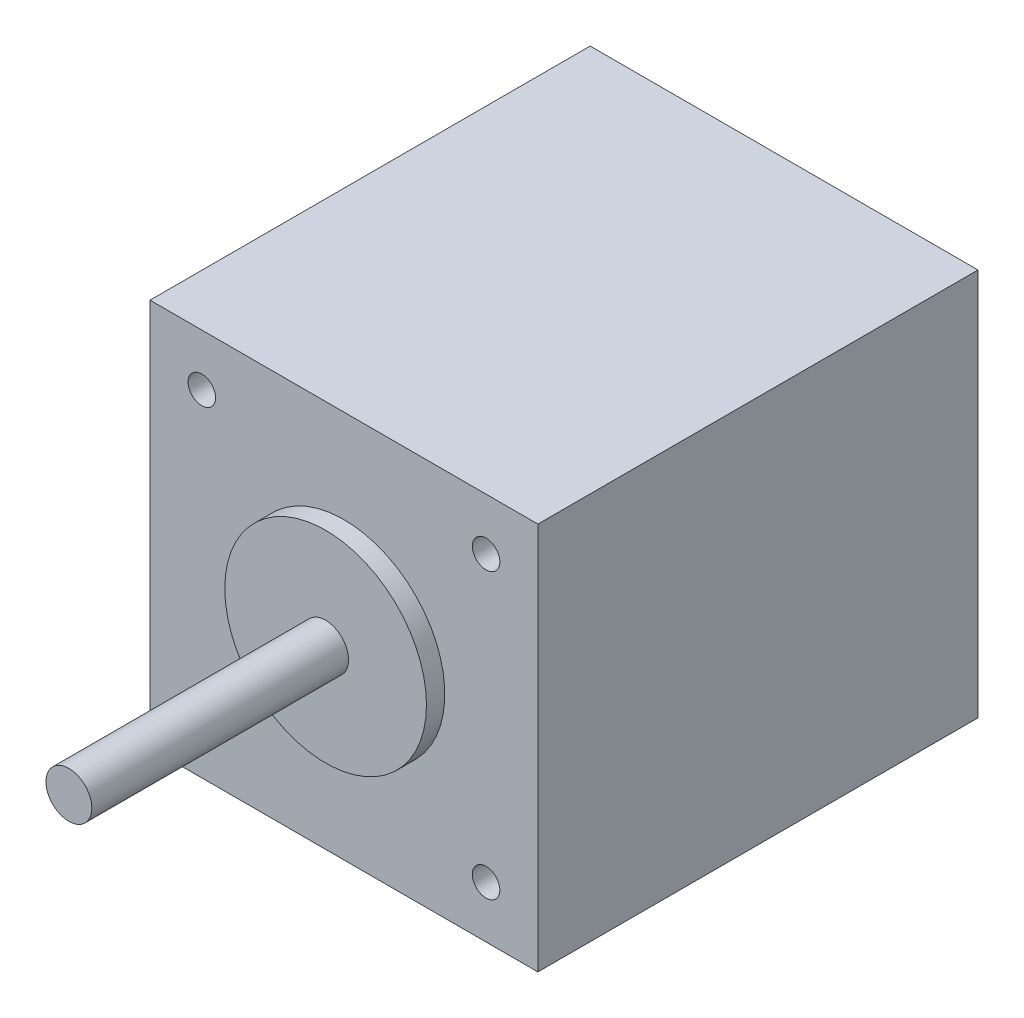
SolidWorks part; units mm, degrees
ref_plane "Спереди" through (0, 0, 0) normal (0, 0, 1) x (1, 0, 0)
ref_plane "Сверху" through (0, 0, 0) normal (0, 1, 0) x (1, 0, 0)
ref_plane "Справа" through (0, 0, 0) normal (1, 0, 0) x (0, 0, -1)
other "Configuration Table"
sketch "Эскиз1" plane through (0, 0, 0) normal (0, 0, 1) x (1, 0, 0)
  line L1 (-21.15, -21.15) -> (21.15, -21.15)
  line L2 (-21.15, -21.15) -> (-21.15, 21.15)
  line L3 (-21.15, 21.15) -> (21.15, 21.15)
  line L4 (21.15, -21.15) -> (21.15, 21.15)
  line L5 (-21.15, -21.15) -> (21.15, 21.15) construction
  line L6 (-21.15, 21.15) -> (21.15, -21.15) construction
  point P0 (0, 0)
  dimension "D1" = 42.3
  dimension "D2" = 42.3
extrude "Корпус" add sketch "Эскиз1" along normal blind 48
sketch "Эскиз2" plane through (0, 0, 0) normal (0, 0, 1) x (1, 0, 0)
  circle A0 centre (0, 0) radius 2.5
extrude "Вал_ПРЕДВ" add sketch "Эскиз2" along normal blind 78
sketch "Эскиз3" plane through (0, 0, 0) normal (0, 0, 1) x (1, 0, 0)
  circle A0 centre (0, 0) radius 11
  dimension "D1" = 22
extrude "Буртик_ПРЕДВ" add sketch "Эскиз3" along normal blind 50
sketch "Эскиз4" plane through (0, 0, 0) normal (0, 0, 1) x (1, 0, 0)
  circle A0 centre (0, 0) radius 8
  dimension "D1" = 16
sketch "Эскиз5" plane through (0, 0, 0) normal (0, 0, 1) x (1, 0, 0)
  circle A0 centre (-15.5, -15.5) radius 1.5
  circle A1 centre (-15.5, 15.5) radius 1.5
  circle A2 centre (15.5, -15.5) radius 1.5
  circle A3 centre (15.5, 15.5) radius 1.5
  dimension "D2" = 3
  dimension "D3" = 3
  dimension "D4" = 3
extrude "Крепеж_М3_ПРЕДВ" cut sketch "Эскиз5" against normal blind 4.5 from offset 48
equation "\"Мотор X ширина корпуса\"= 42.3"
equation "\"Мотор X высота корпуса\"= 42.3"
equation "\"Мотор X длина корпуса\"= 40"
equation "\"Мотор X вылет вала\"= 19.8"
equation "\"Мотор Y ширина корпуса\"= 42.3"
equation "\"Мотор Y высота корпуса\"= 42.3"
equation "\"Мотор Y длина корпуса\"= 48"
equation "\"Мотор Y вылет вала\"= 30"
equation "\"Мотор Z ширина корпуса\"= 42"
equation "\"Мотор Z высота корпуса\"= 42"
equation "\"Мотор Z длина корпуса\"= 40"
equation "\"Мотор Z вылет вала\"= 23"
equation "\"Мотор диаметр вала ПРЕДВ\"= 5"
equation "\"Мотор шаг крепления ПРЕДВ\"= 31"
equation "\"Мотор диаметр отверстий ПРЕДВ\"= 3"
equation "\"Мотор глубина отверстий ПРЕДВ\"= 4.5"
equation "\"Мотор диаметр буртика ПРЕДВ\"= 22"
equation "\"Мотор высота буртика ПРЕДВ\"= 2"
equation "\"Мотор диаметр шкива ПРЕДВ\"= 16"
equation "\"Мотор длина шкива ПРЕДВ\"= 12"
equation "\"Мотор отступ шкива ПРЕДВ\"= 5"
equation "\"Мотор X шаг градусов\"= 1.8"
equation "\"Мотор Y шаг градусов\"= 1.8"
equation "\"Мотор Z шаг градусов\"= 1.8"
equation "\"Мотор Y диаметр ротора\"= 25.78"
equation "\"D1@Эскиз1\" = \"Мотор Y ширина корпуса\""
equation "\"D1@Корпус\" = \"Мотор Y длина корпуса\""
equation "\"D1@Эскиз2\" = \"Мотор диаметр вала ПРЕДВ\""
equation "\"D1@Вал_ПРЕДВ\" = \"Мотор Y длина корпуса\" + \"Мотор Y вылет вала\""
equation "\"D1@Эскиз3\" = \"Мотор диаметр буртика ПРЕДВ\""
equation "\"D1@Буртик_ПРЕДВ\" = \"Мотор Y длина корпуса\" + \"Мотор высота буртика ПРЕДВ\""
equation "\"D1@Эскиз4\" = \"Мотор диаметр шкива ПРЕДВ\""
equation "\"D1@Эскиз5\" = \"Мотор диаметр отверстий ПРЕДВ\""
equation "\"D2@Эскиз5\" = \"Мотор диаметр отверстий ПРЕДВ\""
equation "\"D3@Эскиз5\" = \"Мотор диаметр отверстий ПРЕДВ\""
equation "\"D4@Эскиз5\" = \"Мотор диаметр отверстий ПРЕДВ\""
equation "\"D1@Крепеж_М3_ПРЕДВ\" = \"Мотор глубина отверстий ПРЕДВ\""
equation "\"D19@Крепеж_М3_ПРЕДВ\" = \"Мотор Y длина корпуса\""
equation "\"Ширина груза\"= 160"
equation "\"Глубина груза\"= 240"
equation "\"Высота груза\"= 160"
equation "\"Ширина ячейки\"= \"Ширина груза\" + 10"
equation "\"Глубина ячейки\"= \"Глубина груза\" + 10"
equation "\"Высота ячейки\"= \"Высота груза\" + 10 + 13"
equation "\"Колво ячеек ширина\"= 2"
equation "\"Колво ячеек высота\"= 2"
equation "\"Толщина стенки\" = \"Толщина тонких панелей\""
equation "\"Крепление дверцы\"= 5 "
equation "\"Ширина рейки\"= \"Толщина шестерни\""
equation "\"Высота рейки\"= 20"
equation "\"Высота пола\" = 2*\"Толщина тонких панелей\""
equation "\"Колво полозьев\"= 5"
equation "\"Отступ рейки\"= 20"
equation "\"Глубина каретки\"= \"Глубина ячейки\" + 30 + \"Мотор Y высота корпуса\" + 20"
equation "\"Отступ шпильки\"= 26"
equation "\"Диаметр шпильки\"= 5"
equation "\"Длинна шпильки\" = (\"Высота ячейки\"+\"Толщина горизонтальных плит\"+\"Высота пола\")*\"Колво ячеек высота\"+2*(\"Толщина горизонтальных плит\"+\"Отступ рейки\")"
equation "\"Ширина пластины\"= 50  "
equation "\"Высота зона выгрузки\"= \"Высота ячейки\" * 2 + \"Толщина стенки\" * 2"
equation "\"Колво выгрузки\"= 1"
equation "\"Отступ крепления мотора фиксации\" = (\"Ширина пластины\"+20-\"Толщина вертикальных стенок\")/2"
equation "\"Ширина ячейки выгрузки\" = \"Ширина ячейки\"+\"Толщина вертикальных стенок\"+2*\"Отступ крепления мотора фиксации\""
equation "\"Длинна рейки\" = (\"Ширина ячейки\"+\"Толщина вертикальных стенок\"+\"Крепление дверцы\")*\"Колво ячеек ширина\"+\"Ширина ячейки выгрузки\"*\"Колво выгрузки\"+\"Толщина вертикальных стенок\"+2*\"Отступ крепления мотора фиксации\"-\"Крепление дверцы\"*\"Колво ячеек ширина\""
equation "\"Толщина шестерни\"= 10"
equation "\"Толщина тонких панелей\" = 6"
equation "\"Толщина вертикальных стенок\" = 6"
equation "\"Толщина горизонтальных плит\" = 6"
equation "\"Базовая высота корпуса\"= (\"Высота ячейки\"+\"Толщина тонких панелей\"+\"Высота пола\")*\"Колво ячеек высота\"+6*\"Толщина тонких панелей\"+\"Мотор X ширина корпуса\"+\"Мотор Y ширина корпуса\"+75"
equation "\"Высота корпуса\"= (\"Высота ячейки\"+\"Толщина горизонтальных плит\"+\"Высота пола\")*\"Колво ячеек высота\"+2*\"Толщина горизонтальных плит\"+4*\"Толщина тонких панелей\"+\"Мотор X ширина корпуса\"+\"Мотор Y ширина корпуса\"+75"
equation "\"Смещение центра корпуса\"= (\"Высота корпуса\"-\"Базовая высота корпуса\")/2-(\"Толщина горизонтальных плит\"-\"Толщина тонких панелей\")"
equation "\"Отметка пола\"= -\"Базовая высота корпуса\"/2+\"Толщина тонких панелей\""
equation "\"Отметка потолка\"= \"Отметка пола\"+\"Высота корпуса\"-2*\"Толщина горизонтальных плит\""
equation "\"Отметка верхней полки\"= \"Отметка потолка\"-(28+\"Толщина тонких панелей\")-\"Высота ячейки\"-\"Высота пола\""
equation "\"Отметка нижней полки\"= \"Отметка верхней полки\"-\"Высота ячейки\"-\"Высота пола\"-\"Толщина горизонтальных плит\""
